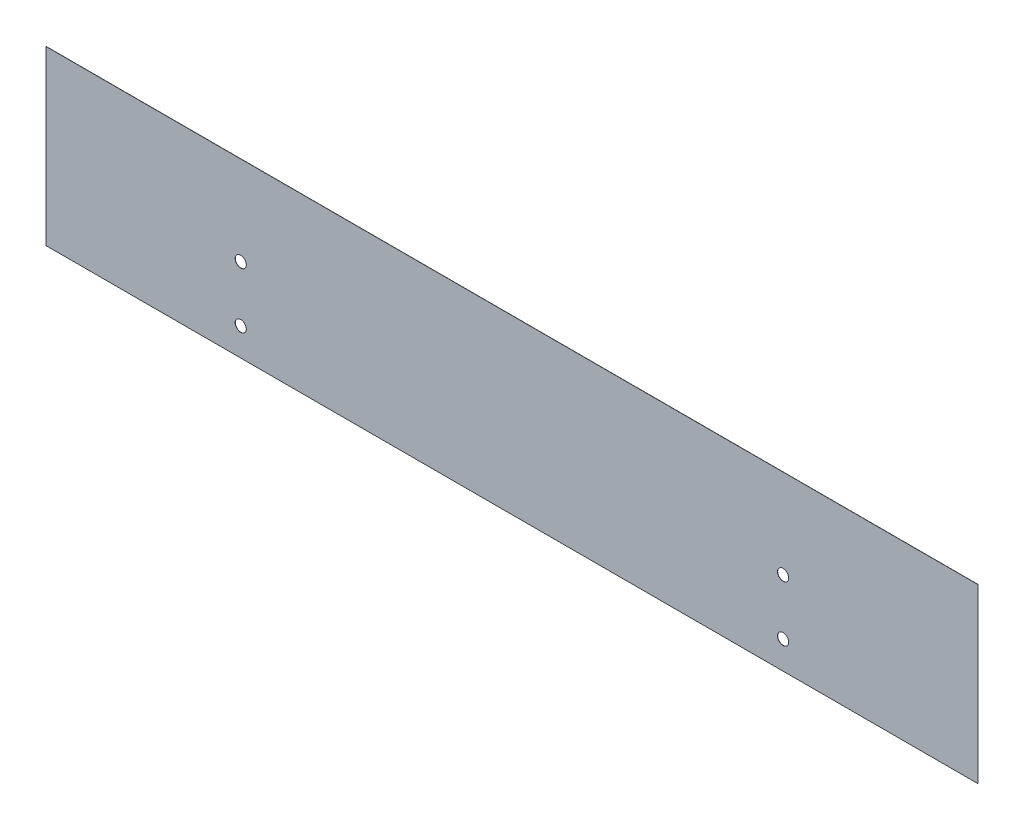
SolidWorks part; units mm, degrees
ref_plane "Front Plane" through (0, 0, 0) normal (0, 0, 1) x (1, 0, 0)
ref_plane "Top Plane" through (0, 0, 0) normal (0, 1, 0) x (1, 0, 0)
ref_plane "Right Plane" through (0, 0, 0) normal (1, 0, 0) x (0, 0, -1)
sketch "Sketch1" plane through (0, 0, 0) normal (0, 0, 1) x (1, 0, 0)
  line L1 (-167.5, -31) -> (167.5, -31)
  line L2 (-167.5, -31) -> (-167.5, 31)
  line L3 (-167.5, 31) -> (167.5, 31)
  line L4 (167.5, -31) -> (167.5, 31)
  line L5 (-167.5, -31) -> (167.5, 31) construction
  line L6 (-167.5, 31) -> (167.5, -31) construction
  point P0 (0, 0)
  dimension "D1" = 335
  dimension "D2" = 62
extrude "Body" add sketch "Sketch1" along normal blind 0.0625
sketch "Sketch2" plane through (0, 0, 0.0625) normal (0, 0, 1) x (1, 0, 0)
  line L0 (-61.5, -1) -> (61.5, -1) construction
  line L1 (61.5, -1) -> (61.5, -21) construction
  line L2 (61.5, -21) -> (-61.5, -21) construction
  line L3 (-61.5, -21) -> (-61.5, -1) construction
  line L4 (0, -1) -> (0, -21) construction
  line L5 (-167.5, -31) -> (167.5, -31) construction
  circle A0 centre (-61.5, -1) radius 2
  circle A1 centre (-61.5, -21) radius 2
  circle A2 centre (61.5, -1) radius 2
  circle A3 centre (61.5, -21) radius 2
  point P10 (-1.1786, -15.4224)
  dimension "D4" = 4
  dimension "D1" = 123
  dimension "D2" = 20
  dimension "D3" = 10
extrude "Camera Mounting holes" [suppressed] cut sketch "Sketch2" against normal blind 0.0625
sketch "Sketch3" plane through (0, 0, 0.0625) normal (0, 0, 1) x (1, 0, 0)
  line L0 (-97.5, -1) -> (97.5, -1) construction
  line L1 (-97.5, -21) -> (97.5, -21) construction
  line L2 (-97.5, -1) -> (-97.5, -21) construction
  line L3 (97.5, -1) -> (97.5, -21) construction
  line L4 (-167.5, -31) -> (167.5, -31) construction
  line L5 (-167.5, 31) -> (-167.5, -31) construction
  line L6 (167.5, -31) -> (167.5, 31) construction
  circle A0 centre (-97.5, -1) radius 2
  circle A1 centre (-97.5, -21) radius 2
  circle A2 centre (97.5, -1) radius 2
  circle A3 centre (97.5, -21) radius 2
  dimension "D1" = 4
  dimension "D2" = 10
  dimension "D3" = 20
  dimension "D4" = 70
  dimension "D5" = 70
extrude "Mounting Holes" cut sketch "Sketch3" against normal blind 0.0625
